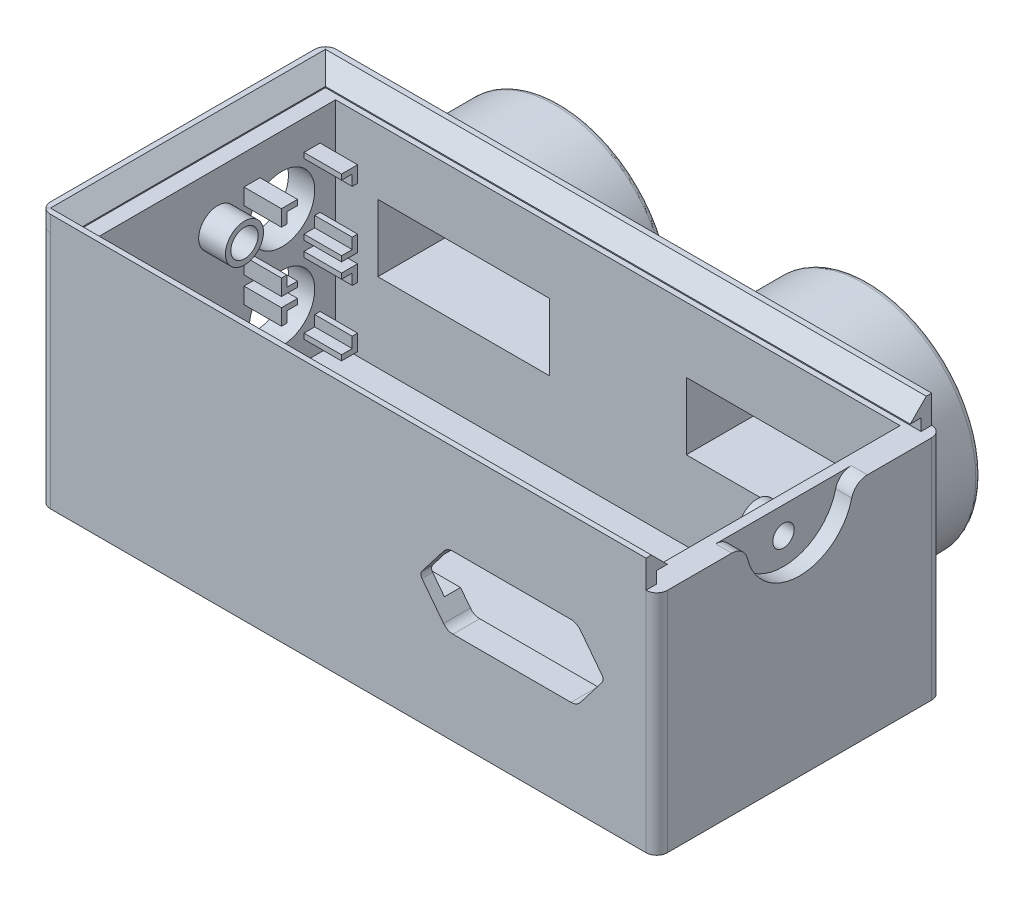
SolidWorks part; units mm, degrees
ref_plane "Front Plane" through (0, 0, 0) normal (0, 0, 1) x (1, 0, 0)
ref_plane "Top Plane" through (0, 0, 0) normal (0, 1, 0) x (1, 0, 0)
ref_plane "Right Plane" through (0, 0, 0) normal (1, 0, 0) x (0, 0, -1)
sketch "Sketch1" plane through (0, 0, 0) normal (0, 1, 0) x (1, 0, 0)
  line L1 (57.55, -25.65) -> (-57.55, -25.65)
  line L2 (57.55, -25.65) -> (57.55, 25.65)
  line L3 (57.55, 25.65) -> (-57.55, 25.65)
  line L4 (-57.55, -25.65) -> (-57.55, 25.65)
  line L5 (57.55, -25.65) -> (-57.55, 25.65) construction
  line L6 (57.55, 25.65) -> (-57.55, -25.65) construction
  point P0 (0, 0)
  dimension "D1" = 115.1
  dimension "D2" = 51.3
extrude "Boss-Extrude1" add sketch "Sketch1" along normal blind 3
sketch "Sketch2" plane through (0, 3, 0) normal (0, 1, 0) x (1, 0, 0)
  line L1 (52.65, -22.65) -> (-52.65, -22.65)
  line L2 (52.65, -22.65) -> (52.65, 22.65)
  line L3 (52.65, 22.65) -> (-52.65, 22.65)
  line L4 (-52.65, -22.65) -> (-52.65, 22.65)
  line L5 (52.65, -22.65) -> (-52.65, 22.65) construction
  line L6 (52.65, 22.65) -> (-52.65, -22.65) construction
  line L7 (57.55, 25.65) -> (-57.55, 25.65)
  line L8 (57.55, 25.65) -> (57.55, -25.65)
  line L9 (57.55, -25.65) -> (-57.55, -25.65)
  line L10 (-57.55, 25.65) -> (-57.55, -25.65)
  line L11 (57.55, 25.65) -> (-57.55, -25.65) construction
  line L12 (57.55, -25.65) -> (-57.55, 25.65) construction
  point P0 (0, 0)
  point P6 (0, 0)
  dimension "D1" = 105.3
  dimension "D2" = 45.3
extrude "Boss-Extrude2" add sketch "Sketch2" along normal blind 45
sketch "Sketch5" plane through (0, 0, -25.65) normal (0, 0, -1) x (-1, 0, 0)
  line L0 (0, 48) -> (0, 0) construction
  line L1 (-57.55, 48) -> (57.55, 48) construction
  line L2 (-57.55, 48) -> (0, 48) construction
  line L3 (-28.775, 48) -> (-28.775, 0) construction
  line L4 (-57.55, 0) -> (57.55, 0) construction
  line L5 (44.775, 17.75) -> (12.775, 17.75)
  line L6 (-44.775, 30.25) -> (-12.775, 30.25)
  line L7 (-44.775, 30.25) -> (-44.775, 17.75)
  line L8 (-44.775, 17.75) -> (-12.775, 17.75)
  line L9 (-12.775, 30.25) -> (-12.775, 17.75)
  line L10 (-44.775, 30.25) -> (-12.775, 17.75) construction
  line L11 (-44.775, 17.75) -> (-12.775, 30.25) construction
  line L12 (12.775, 30.25) -> (12.775, 17.75)
  line L13 (44.775, 30.25) -> (12.775, 30.25)
  line L14 (44.775, 30.25) -> (44.775, 17.75)
  circle A0 centre (-28.775, 24) radius 21
  circle A1 centre (28.775, 24) radius 21
  point P24 (0, 24)
  point P27 (-28.775, 3)
  dimension "D1" = 42
  dimension "D2" = 32
  dimension "D3" = 12.5
extrude "Boss-Extrude4" add sketch "Sketch5" along normal blind 15
sketch "Sketch10" plane through (0, 0, 25.65) normal (0, 0, 1) x (1, 0, 0)
  line L4 (-57.55, 0) -> (57.55, 0)
  line L5 (57.55, 0) -> (57.55, 48)
  line L6 (57.55, 48) -> (-57.55, 48)
  line L7 (-57.55, 48) -> (-57.55, 0)
  line L8 (-57.55, 0) -> (57.55, 0)
  line L9 (57.55, 0) -> (57.55, 48)
  line L10 (57.55, 48) -> (-57.55, 48)
  line L11 (-57.55, 48) -> (-57.55, 0)
  dimension "D1" = 0
extrude "Boss-Extrude7" add sketch "Sketch10" along normal blind 2
sketch "Sketch11" plane through (0, 0, -25.65) normal (0, 0, -1) x (-1, 0, 0)
  line L0 (12.775, 17.75) -> (44.775, 17.75) construction
  line L1 (44.775, 17.75) -> (44.775, 30.25) construction
  line L2 (44.775, 30.25) -> (12.775, 30.25) construction
  line L3 (12.775, 30.25) -> (12.775, 17.75) construction
  line L4 (-44.775, 17.75) -> (-12.775, 17.75) construction
  line L5 (-12.775, 17.75) -> (-12.775, 30.25) construction
  line L6 (-12.775, 30.25) -> (-44.775, 30.25) construction
  line L7 (-44.775, 30.25) -> (-44.775, 17.75) construction
  line L8 (12.775, 17.75) -> (44.775, 17.75)
  line L9 (44.775, 17.75) -> (44.775, 30.25)
  line L10 (44.775, 30.25) -> (12.775, 30.25)
  line L11 (12.775, 30.25) -> (12.775, 17.75)
  line L12 (-44.775, 17.75) -> (-12.775, 17.75)
  line L13 (-12.775, 17.75) -> (-12.775, 30.25)
  line L14 (-12.775, 30.25) -> (-44.775, 30.25)
  line L15 (-44.775, 30.25) -> (-44.775, 17.75)
extrude "Cut-Extrude1" cut sketch "Sketch11" against normal blind 12
sketch "Sketch12" plane through (0, 0, -40.65) normal (0, 0, -1) x (-1, 0, 0)
  line L0 (0, 48) -> (0, 0) construction
  line L2 (-44.775, 30.25) -> (-12.775, 17.75) construction
  line L3 (-57.55, 48) -> (57.55, 48) construction
  line L5 (-47.275, 31.6) -> (-10.275, 31.6)
  line L6 (-47.275, 31.6) -> (-47.275, 16.4)
  line L7 (-47.275, 16.4) -> (-10.275, 16.4)
  line L8 (-10.275, 31.6) -> (-10.275, 16.4)
  line L9 (-47.275, 31.6) -> (-10.275, 16.4) construction
  line L10 (-47.275, 16.4) -> (-10.275, 31.6) construction
  line L14 (47.275, 16.4) -> (10.275, 16.4)
  line L15 (10.275, 31.6) -> (10.275, 16.4)
  line L16 (47.275, 31.6) -> (10.275, 31.6)
  line L17 (47.275, 31.6) -> (47.275, 16.4)
  point P7 (-28.775, 24)
  dimension "D1" = 37
  dimension "D2" = 15.2
extrude "Cut-Extrude2" cut sketch "Sketch12" against normal blind 3
fillet "Fillet1" radius 1 4 edges at (7.775, 24, -40.65) (-7.775, 24, -25.65) (7.775, 24, -25.65) (-7.775, 24, -40.65)
fillet "Fillet2" radius 2 4 edges at (57.55, 24, -25.65) (57.55, 24, 27.65) (-57.55, 24, 27.65) (-57.55, 24, -25.65)
sketch "Sketch14" plane through (-57.55, 0, 0) normal (-1, 0, 0) x (0, 0, 1)
  line L3 (-22.65, 48) -> (-22.65, 3) construction
  circle A0 centre (-12.65, 29.75) radius 6.1
  circle A1 centre (-12.65, 13.75) radius 6.1
  circle A2 centre (-0.65, 32.75) radius 2.55
  dimension "D1" = 12.2
  dimension "D3" = 5.1
  dimension "D6" = 12.2
  dimension "D2" = 3
  dimension "D4" = 12
  dimension "D5" = 10
extrude "Cut-Extrude4" cut sketch "Sketch14" against normal blind 5
sketch "Sketch16" plane through (-57.55, 0, 0) normal (-1, 0, 0) x (0, 0, 1)
  circle A2 centre (-0.65, 32.75) radius 3.55
  circle A3 centre (-0.65, 32.75) radius 3.55
  dimension "D1" = 1
extrude "Cut-Extrude5" cut sketch "Sketch16" against normal blind 1
sketch "Sketch17" plane through (0, 0, 27.65) normal (0, 0, 1) x (1, 0, 0)
  line L0 (30.55, 24) -> (47.55, 24) construction
  line L1 (41.5652, 17.5) -> (19.5348, 17.5) construction
  line L2 (42.55, 17.5) -> (42.55, 30.5)
  line L3 (41.5652, 30.5) -> (19.5348, 30.5) construction
  line L4 (18.55, 17.5) -> (18.55, 30.5)
  line L5 (42.55, 17.5) -> (18.55, 30.5) construction
  line L6 (42.55, 30.5) -> (18.55, 17.5) construction
  line L7 (43.1504, 29.7194) -> (45.05, 27.25) construction
  line L8 (45.05, 20.75) -> (43.1504, 18.2806) construction
  line L9 (30.55, 30.5) -> (30.55, 17.5) construction
  line L10 (16.05, 20.75) -> (17.9496, 18.2806) construction
  line L11 (17.9496, 29.7194) -> (16.05, 27.25) construction
  line L12 (-55.55, 0) -> (55.55, 0) construction
  line L15 (55.55, 0) -> (55.55, 48) construction
  line L16 (45.05, 27.25) -> (52.05, 27.25) construction
  line L17 (45.05, 20.75) -> (52.05, 20.75) construction
  line L18 (52.05, 20.75) -> (52.05, 27.25) construction
  line L19 (45.0267, 24) -> (52.05, 24) construction
  line L20 (16.05, 20.75) -> (9.05, 20.75) construction
  line L21 (9.05, 20.75) -> (9.05, 27.25) construction
  line L22 (16.05, 27.25) -> (9.05, 27.25) construction
  line L23 (15.9515, 20.55) -> (17.791, 18.1586)
  line L24 (41.5652, 17.3) -> (19.5348, 17.3)
  line L25 (45.1485, 20.55) -> (43.309, 18.1586)
  line L26 (45.1485, 20.55) -> (52.25, 20.55)
  line L27 (52.25, 20.55) -> (52.25, 27.45)
  line L28 (45.1485, 27.45) -> (52.25, 27.45)
  line L29 (43.309, 29.8414) -> (45.1485, 27.45)
  line L30 (41.5652, 30.7) -> (19.5348, 30.7)
  line L31 (17.791, 29.8414) -> (15.9515, 27.45)
  line L32 (15.9515, 27.45) -> (8.85, 27.45)
  line L33 (8.85, 20.55) -> (8.85, 27.45)
  line L34 (15.9515, 20.55) -> (8.85, 20.55)
  arc A0 (17.9496, 18.2806) -> (19.5348, 17.5) centre (19.5348, 19.5) ccw construction
  arc A2 (19.5348, 30.5) -> (17.9496, 29.7194) centre (19.5348, 28.5) ccw construction
  arc A3 (41.5652, 17.5) -> (43.1504, 18.2806) centre (41.5652, 19.5) ccw construction
  arc A5 (41.5652, 30.5) -> (43.1504, 29.7194) centre (41.5652, 28.5) cw construction
  circle A6 centre (48.5384, 24) radius 1.6 construction
  circle A7 centre (12.5616, 24) radius 1.6 construction
  arc A8 (17.791, 18.1586) -> (19.5348, 17.3) centre (19.5348, 19.5) ccw
  arc A9 (41.5652, 17.3) -> (43.309, 18.1586) centre (41.5652, 19.5) ccw
  arc A10 (41.5652, 30.7) -> (43.309, 29.8414) centre (41.5652, 28.5) cw
  arc A11 (19.5348, 30.7) -> (17.791, 29.8414) centre (19.5348, 28.5) ccw
  point P0 (30.55, 24)
  point P24 (13.55, 24)
  dimension "D5" = 2
  dimension "D7" = 3.2
  dimension "D1" = 24
  dimension "D2" = 13
  dimension "D3" = 17
  dimension "D4" = 25
  dimension "D6" = 7
  dimension "D8" = 6.5
  dimension "D10" = 24
  dimension "D9" = 0.2
sketch "Sketch18" plane through (-52.65, 0, 0) normal (1, 0, 0) x (0, 0, -1)
  circle A0 centre (0.65, 32.75) radius 2.55 construction
  circle A1 centre (0.65, 32.75) radius 2.55
  circle A2 centre (0.65, 32.75) radius 3.55
  dimension "D1" = 1
extrude "Boss-Extrude9" add sketch "Sketch18" along normal blind 5
extrude "Cut-Extrude6" cut sketch "Sketch17" against normal blind 5 contours L4 L1 L2 L3 | L8 L7 L2 | L4 L11 L10 region at (30.55, 24, 27.65) region at (46.9492, 24, 27.65) region at (14.1508, 24, 27.65)
sketch "Sketch23" plane through (-52.65, 0, 0) normal (1, 0, 0) x (0, 0, -1)
  line L0 (12.65, 21.75) -> (12.65, 19.85) construction
  line L7 (5.55, 33.85) -> (6.55, 33.85)
  line L8 (6.55, 35.85) -> (8.55, 35.85)
  line L13 (6.55, 35.85) -> (6.55, 33.85)
  line L14 (6.55, 23.65) -> (8.55, 23.65)
  line L19 (18.75, 35.85) -> (18.75, 33.85)
  line L20 (5.55, 25.65) -> (5.55, 22.65)
  line L24 (6.55, 25.65) -> (6.55, 23.65)
  line L25 (5.55, 36.85) -> (8.55, 36.85)
  line L26 (5.55, 36.85) -> (5.55, 33.85)
  line L27 (5.55, 22.65) -> (8.55, 22.65)
  line L28 (19.75, 36.85) -> (19.75, 33.85)
  line L29 (16.75, 36.85) -> (19.75, 36.85)
  line L30 (16.75, 35.85) -> (18.75, 35.85)
  line L31 (8.55, 36.85) -> (8.55, 35.85)
  line L32 (16.75, 22.65) -> (16.75, 23.65)
  line L33 (19.75, 25.65) -> (18.75, 25.65)
  line L34 (16.75, 36.85) -> (16.75, 35.85)
  line L35 (19.75, 33.85) -> (18.75, 33.85)
  line L36 (8.55, 22.65) -> (8.55, 23.65)
  line L37 (5.55, 25.65) -> (6.55, 25.65)
  line L38 (19.75, 6.65) -> (19.75, 9.65)
  line L39 (5.55, 20.85) -> (8.55, 20.85)
  line L40 (5.55, 6.65) -> (5.55, 9.65)
  line L41 (5.55, 6.65) -> (8.55, 6.65)
  line L42 (6.55, 19.85) -> (8.55, 19.85)
  line L43 (18.75, 7.65) -> (18.75, 9.65)
  line L44 (6.55, 7.65) -> (8.55, 7.65)
  line L45 (6.55, 7.65) -> (6.55, 9.65)
  line L46 (8.55, 20.85) -> (8.55, 19.85)
  line L47 (16.75, 20.85) -> (16.75, 19.85)
  line L48 (19.75, 17.85) -> (18.75, 17.85)
  line L49 (19.75, 9.65) -> (18.75, 9.65)
  line L50 (16.75, 6.65) -> (16.75, 7.65)
  line L51 (8.55, 6.65) -> (8.55, 7.65)
  line L53 (5.55, 9.65) -> (6.55, 9.65)
  line L54 (5.55, 17.85) -> (6.55, 17.85)
  line L55 (16.75, 23.65) -> (18.75, 23.65)
  line L56 (16.75, 22.65) -> (19.75, 22.65)
  line L57 (18.75, 25.65) -> (18.75, 23.65)
  line L58 (19.75, 25.65) -> (19.75, 22.65)
  line L59 (6.55, 17.85) -> (6.55, 19.85)
  line L60 (5.55, 17.85) -> (5.55, 20.85)
  line L61 (16.75, 7.65) -> (18.75, 7.65)
  line L62 (16.75, 6.65) -> (19.75, 6.65)
  line L63 (19.75, 17.85) -> (19.75, 20.85)
  line L64 (18.75, 17.85) -> (18.75, 19.85)
  line L65 (16.75, 20.85) -> (19.75, 20.85)
  line L66 (16.75, 19.85) -> (18.75, 19.85)
  circle A2 centre (12.65, 13.75) radius 6.1 construction
  point P6 (12.65, 29.75)
  point P9 (12.65, 20.8)
  point P14 (12.65, 29.75)
  dimension "D1" = 12.2
  dimension "D2" = 12.2
  dimension "D4" = 14.2
  dimension "D5" = 3
  dimension "D3" = 14.2
  dimension "D6" = 3
extrude "Boss-Extrude10" add sketch "Sketch23" along normal blind 7
sketch "Sketch25" plane through (0, 0, 27.65) normal (0, 0, 1) x (1, 0, 0)
  line L0 (15.9515, 27.45) -> (13.7667, 24.6097)
  line L1 (13.7667, 23.3903) -> (15.9515, 20.55)
  line L2 (45.1485, 27.45) -> (47.3333, 24.6097)
  line L3 (47.3333, 23.3903) -> (45.1485, 20.55)
  line L4 (15.9515, 20.55) -> (17.791, 18.1586) construction
  line L5 (17.791, 29.8414) -> (15.9515, 27.45) construction
  line L6 (8.85, 20.55) -> (8.85, 27.45) construction
  line L7 (43.309, 29.8414) -> (45.1485, 27.45) construction
  line L8 (45.1485, 20.55) -> (43.309, 18.1586) construction
  line L9 (52.25, 20.55) -> (52.25, 27.45) construction
  line L10 (45.1485, 27.45) -> (52.25, 27.45) construction
  line L11 (45.1485, 20.55) -> (52.25, 20.55) construction
  line L12 (15.9515, 20.55) -> (8.85, 20.55) construction
  line L13 (15.9515, 27.45) -> (8.85, 27.45) construction
  line L14 (52.25, 20.55) -> (52.25, 27.45)
  line L15 (45.1485, 27.45) -> (52.25, 27.45)
  line L16 (45.1485, 20.55) -> (52.25, 20.55)
  line L17 (15.9515, 20.55) -> (8.85, 20.55)
  line L18 (8.85, 20.55) -> (8.85, 27.45)
  line L19 (15.9515, 27.45) -> (8.85, 27.45)
  arc A0 (47.3333, 24.6097) -> (47.3333, 23.3903) centre (46.5407, 24) cw
  arc A1 (13.7667, 24.6097) -> (13.7667, 23.3903) centre (14.5593, 24) ccw
  point P16 (8.85, 24)
  point P26 (13.2977, 24)
  dimension "D1" = 1
extrude "Boss-Extrude11" add sketch "Sketch25" against normal blind 2
sketch "Sketch28" plane through (57.55, 0, 0) normal (1, 0, 0) x (0, 0, -1)
  line L0 (-25.65, 48) -> (23.65, 48) construction
  line L1 (-25.65, 44.6) -> (23.65, 44.6)
  line L2 (-25.65, 44.6) -> (-25.65, 42.4)
  line L3 (-25.65, 42.4) -> (23.65, 42.4)
  line L4 (23.65, 44.6) -> (23.65, 42.4)
  line L5 (-27.65, 0) -> (-27.65, 48) construction
  line L9 (22.65, 48) -> (22.65, 3) construction
  point P4 (-25.65, 43.5)
  dimension "D1" = 2.2
  dimension "D2" = 2
  dimension "D3" = 1
  dimension "D4" = 4.5
extrude "Cut-Extrude9" cut sketch "Sketch28" against normal blind 113.1
sketch "Sketch29" plane through (0, 48, 0) normal (0, 1, 0) x (1, 0, 0)
  line L0 (57.55, -25.65) -> (57.55, 23.65) construction
  line L1 (52.65, 22.65) -> (57.55, 22.65)
  line L2 (52.65, 22.65) -> (52.65, -22.65)
  line L3 (52.65, -22.65) -> (57.55, -22.65)
  line L4 (57.55, 22.65) -> (57.55, -22.65)
extrude "Cut-Extrude11" cut sketch "Sketch29" against normal up to surface (5.6 mm away) up to face at (0, 42.4, 0)
sketch "Sketch33" plane through (0, 48, 0) normal (0, 1, 0) x (1, 0, 0)
  line L1 (57.55, 25.65) -> (55.55, 25.65)
  line L2 (57.55, 25.65) -> (57.55, -27.65)
  line L3 (57.55, -27.65) -> (55.55, -27.65)
  line L4 (55.55, 25.65) -> (55.55, -27.65)
  line L5 (57.55, -25.65) -> (57.55, 23.65) construction
  line L6 (55.55, -27.65) -> (-55.55, -27.65) construction
  dimension "D1" = 2
extrude "Cut-Extrude12" cut sketch "Sketch33" against normal up to surface (5.6 mm away) up to face at (0, 42.4, 0)
sketch "Sketch34" plane through (57.55, 0, 0) normal (1, 0, 0) x (0, 0, -1)
  line L1 (-25.65, 42.4) -> (23.65, 42.4) construction
  circle A0 centre (-1, 42.4) radius 10
  point P5 (-1, 42.4)
  dimension "D1" = 20
extrude "Cut-Extrude13" cut sketch "Sketch34" against normal blind 3
fillet "Fillet3" radius 3 2 edges at (56.05, 42.4, -9) (56.05, 42.4, 11)
sketch "Sketch35" plane through (54.55, 0, 0) normal (1, 0, 0) x (0, 0, -1)
  line L0 (-1, 42.4) -> (-1, 32.4) construction
  line L4 (11.6491, 42.4) -> (-13.6491, 42.4) construction
  circle A1 centre (-1, 37.4) radius 2
  arc A3 (-10.7301, 40.0923) -> (8.7301, 40.0923) centre (-1, 42.4) ccw construction
  point P10 (-1, 37.4)
  dimension "D1" = 4
extrude "Cut-Extrude14" cut sketch "Sketch35" against normal blind 3
sketch "Sketch37" plane through (52.65, 0, 0) normal (-1, 0, 0) x (0, 0, 1)
  circle A0 centre (1, 37.4) radius 2 construction
  circle A1 centre (1, 37.4) radius 2
  circle A2 centre (1, 37.4) radius 3.5
  dimension "D1" = 1.5
extrude "Boss-Extrude13" add sketch "Sketch37" along normal blind 3
fillet "Fillet5" radius 1 1 edges at (52.65, 37.4, 4.5)
sketch "Sketch43" plane through (0, 0, -22.65) normal (0, 0, 1) x (1, 0, 0)
  line L4 (55.55, 44.6) -> (55.55, 48)
  line L5 (55.55, 48) -> (-52.65, 48)
  line L6 (-52.65, 48) -> (-52.65, 44.6)
  line L7 (-52.65, 44.6) -> (55.55, 44.6)
  line L8 (55.55, 44.6) -> (55.55, 48)
  line L9 (55.55, 48) -> (-52.65, 48)
  line L10 (-52.65, 48) -> (-52.65, 44.6)
  line L11 (-52.65, 44.6) -> (55.55, 44.6)
  dimension "D1" = 0
extrude "Boss-Extrude14" add sketch "Sketch43" along normal blind 2
sketch "Sketch41" plane through (55.55, 0, 0) normal (1, 0, 0) x (0, 0, -1)
  line L0 (25.65, 48) -> (25.65, 42.4) construction
  line L1 (-27.65, 48) -> (25.65, 48)
  line L2 (-27.65, 48) -> (-27.65, 44.6)
  line L3 (-27.65, 44.6) -> (25.65, 44.6)
  line L4 (25.65, 48) -> (25.65, 44.6)
  line L5 (23.65, 44.6) -> (-25.65, 44.6) construction
extrude "Cut-Extrude16" cut sketch "Sketch41" against normal through all
sketch "Sketch42" plane through (55.55, 0, 0) normal (1, 0, 0) x (0, 0, -1)
  line L0 (-27.65, 44.6) -> (-27.65, 47.6)
  line L1 (-27.65, 47.6) -> (-26.65, 47.6)
  line L2 (-26.65, 47.6) -> (-23.65, 44.6)
  line L3 (23.65, 44.6) -> (-25.65, 44.6) construction
  line L4 (-23.65, 44.6) -> (-27.65, 44.6)
  dimension "D1" = 3
  dimension "D2" = 1
  dimension "D3" = 4
sketch "Sketch44" plane through (0, 44.6, 0) normal (0, 1, 0) x (1, 0, 0)
  line L0 (-55.55, 23.65) -> (55.55, 23.65) construction
  line L1 (-55.55, -25.65) -> (55.55, -25.65) construction
  line L2 (-55.55, 23.65) -> (-55.55, -25.65) construction
  line L3 (-55.55, 23.65) -> (55.55, 23.65)
  line L4 (-55.55, -25.65) -> (55.55, -25.65)
  line L5 (-55.55, 23.65) -> (-55.55, -25.65)
sweep "Sweep2" add profiles "Sketch42" path "Sketch44"
fillet "Fillet7" radius 2 2 edges at (-57.55, 46.1, 27.65) (-57.55, 46.1, -25.65)
